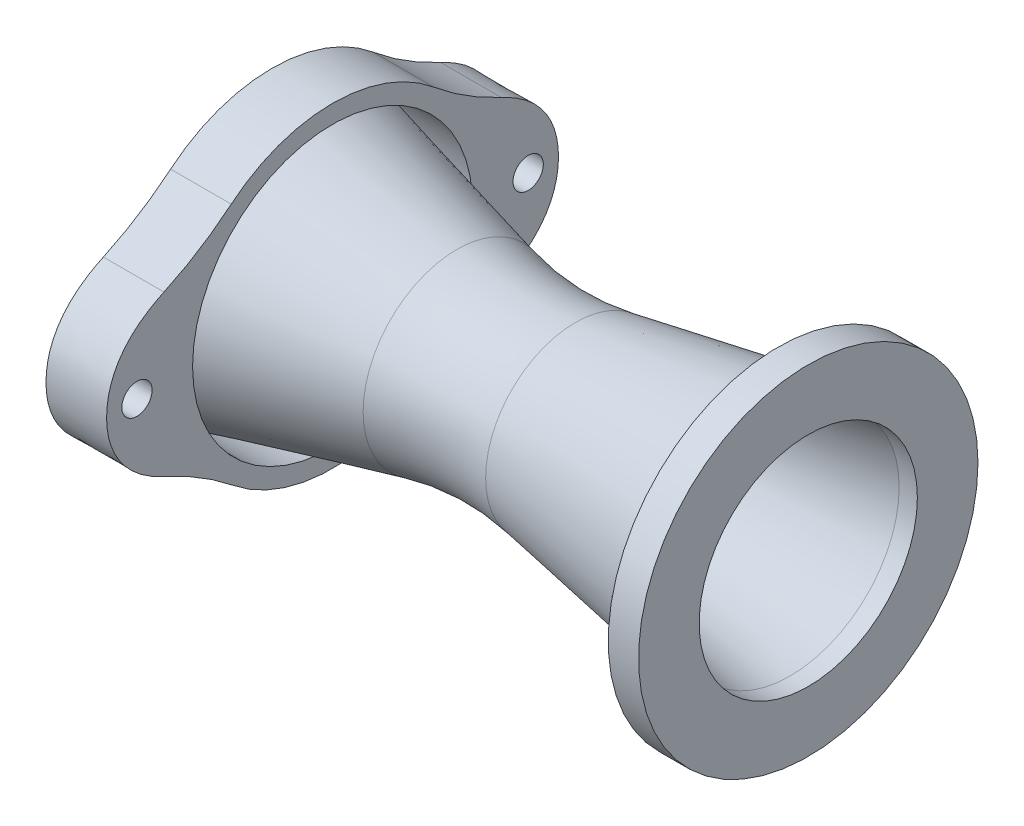
SolidWorks part; units mm, degrees
ref_plane "Front Plane" through (0, 0, 0) normal (0, 0, 1) x (1, 0, 0)
ref_plane "Top Plane" through (0, 0, 0) normal (0, 1, 0) x (1, 0, 0)
ref_plane "Right Plane" through (0, 0, 0) normal (1, 0, 0) x (0, 0, -1)
sketch "Sketch1" plane through (0, 0, 0) normal (0, 0, 1) x (1, 0, 0)
  line L0 (-40.1078, 0) -> (45.3703, 0)
  line L1 (45.3703, 0) -> (45.3703, 18)
  line L2 (45.3703, 18) -> (10.4664, 11.8455)
  line L3 (-10.3121, 12.5711) -> (-40.1078, 20)
  line L4 (-40.1078, 20) -> (-40.1078, 0)
  line L5 (-19.5191, 10) -> (23.6112, 10) construction
  arc A0 (10.4664, 11.8455) -> (-10.3121, 12.5711) centre (1.784, 61.0859) cw
  point P10 (0, 10)
  dimension "D6" = 50
  dimension "D1" = 10
  dimension "D2" = 20
  dimension "D3" = 18
  dimension "D4" = 14
  dimension "D5" = 10
revolve "Revolve1" add sketch "Sketch1" angle 360 about L0
shell "Shell4" thickness 3 removed face at (-40.1078, 0, 20) removed face at (45.3703, 0, 18) outward yes
ref_plane "Plane4" through (-40.1078, 0, 0) normal (-1, 0, 0) x (0, 0, 1)
ref_plane "Plane5" through (45.3703, 0, 0) normal (1, 0, 0) x (0, 0, -1)
sketch "Sketch3" plane through (-40.1078, 0, 0) normal (-1, 0, 0) x (0, 0, 1)
  line L0 (-51.3376, 0) -> (51.3376, 0) construction
  line L1 (0, -5.2194) -> (0, 7.0492) construction
  circle A0 centre (0, 0) radius 23.0918 construction
  circle A1 centre (0, 0) radius 23.0918
  arc A2 (-16.3901, -20.3014) -> (16.3901, -20.3014) centre (0, 0) ccw
  circle A3 centre (0, 0) radius 26.0918 construction
  arc A4 (16.7106, 20.0384) -> (-16.7106, 20.0384) centre (0, 0) ccw
  arc A5 (27.4034, -13.554) -> (16.3901, -20.3014) centre (47.7987, -59.2052) ccw
  arc A6 (27.8084, 13.0274) -> (16.7106, 20.0384) centre (48.7334, 58.4382) cw
  arc A7 (-27.8084, 13.0274) -> (-16.7106, 20.0384) centre (-48.7334, 58.4382) ccw
  arc A8 (-27.4034, -13.554) -> (-16.3901, -20.3014) centre (-47.7987, -59.2052) cw
  circle A9 centre (-32.2697, 0) radius 2.5
  circle A10 centre (32.2697, 0) radius 2.5
  spline S0 degree 3 poles (-27.4034, -13.554) (-34.7427, -10.2751) (-39.8148, -0.1921) (-34.712, 9.8462) (-27.8084, 13.0274) knots 0.087297 0.087297 0.087297 0.087297 0.506663 0.909418 0.909418 0.909418 0.909418
  spline S1 degree 3 poles (27.4034, -13.554) (34.7427, -10.2751) (39.8148, -0.1921) (34.712, 9.8462) (27.8084, 13.0274) knots 0.087297 0.087297 0.087297 0.087297 0.506663 0.909418 0.909418 0.909418 0.909418
  point P6 (0, 0)
  dimension "D2" = 50
  dimension "D3" = 5
  dimension "D4" = 5
  dimension "D5" = 5
  dimension "D6" = 5
  dimension "D1" = 3
extrude "Boss-Extrude1" add sketch "Sketch3" against normal blind 10 separate body
sketch "Sketch4" plane through (45.3703, 0, 0) normal (1, 0, 0) x (0, 0, -1)
  circle A0 centre (0, 0) radius 18 construction
  circle A1 centre (0, 0) radius 18
  circle A2 centre (0, 0) radius 28
  dimension "D1" = 10
extrude "Boss-Extrude2" add sketch "Sketch4" along normal blind 3 and the other way blind 2
